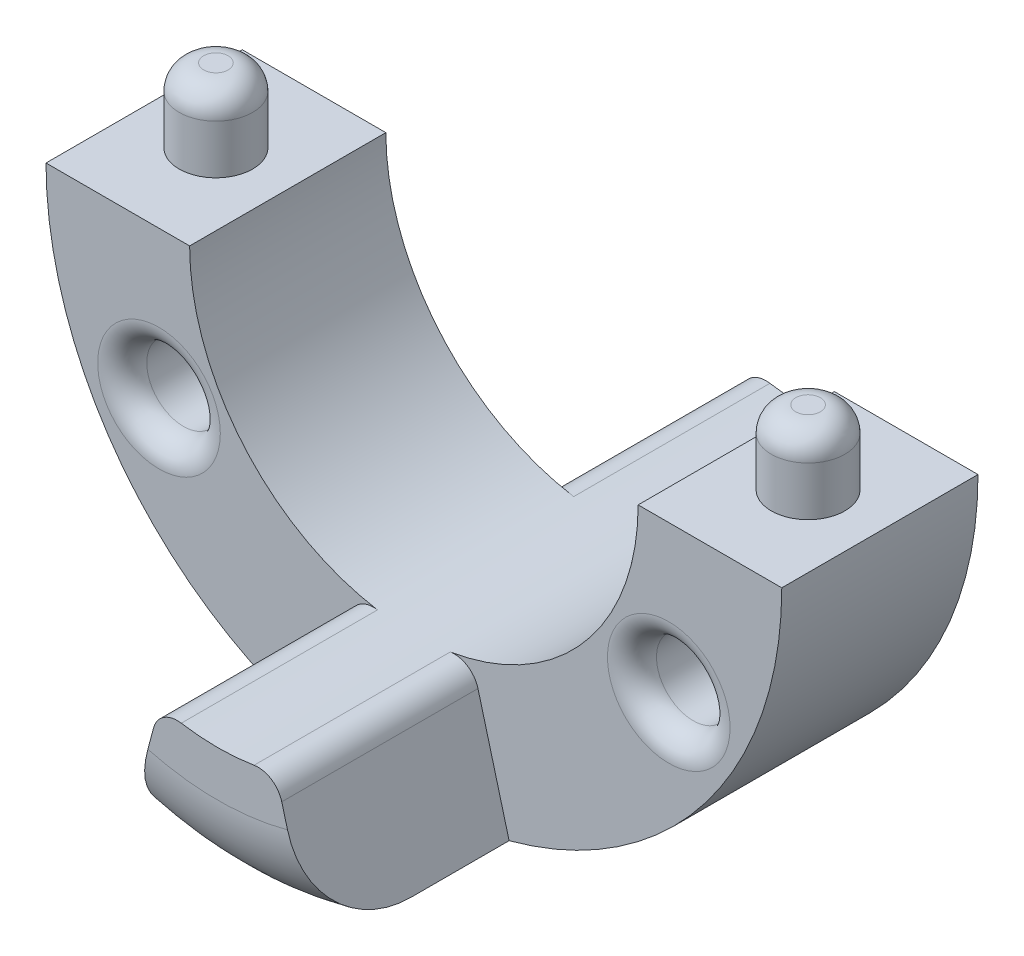
SolidWorks part; units mm, degrees
material "PET"
ref_plane "Front Plane" through (0, 0, 0) normal (0, 0, 1) x (1, 0, 0)
ref_plane "Top Plane" through (0, 0, 0) normal (0, 1, 0) x (1, 0, 0)
ref_plane "Right Plane" through (0, 0, 0) normal (1, 0, 0) x (0, 0, -1)
sketch "Sketch1" plane through (0, 0, 0) normal (0, 0, 1) x (1, 0, 0)
  line L0 (0, 0) -> (0, 2.286) construction
  line L1 (0, 2.625) -> (0, 3) construction
  line L2 (0, 2.625) -> (0, 2.286) construction
  circle A0 centre (0, 0) radius 2.286
  circle A1 centre (0, 0) radius 3.75
  circle A2 centre (0, 3) radius 0.375
  circle A3 centre (2.5981, -1.5) radius 0.375
  circle A4 centre (-2.5981, -1.5) radius 0.375
  point P15 (0, 0)
  dimension "D1" = 4.572
  dimension "D2" = 0.75
  dimension "D4" = 7.5
  dimension "D3" = 3
  dimension "D5" = 3
extrude "Boss-Extrude1" add sketch "Sketch1" along normal blind 2
sketch "Sketch2" plane through (0, 0, 2) normal (0, 0, 1) x (1, 0, 0)
  line L0 (-0.5917, -2.2081) -> (-0.9706, -3.6222)
  line L1 (0, 0) -> (0, -4.001) construction
  line L2 (0.5917, -2.2081) -> (0.9706, -3.6222)
  line L3 (-1.6164, 1.6164) -> (-2.6517, 2.6517)
  line L4 (-2.2081, 0.5917) -> (-3.6222, 0.9706)
  line L5 (2.2081, 0.5917) -> (3.6222, 0.9706)
  line L6 (1.6164, 1.6164) -> (2.6517, 2.6517)
  circle A0 centre (0, 0) radius 3.75 construction
  arc A1 (-0.9706, -3.6222) -> (0.9706, -3.6222) centre (0, 0) ccw
  arc A3 (-0.5917, -2.2081) -> (0.5917, -2.2081) centre (0, 0) ccw
  circle A4 centre (0, 0) radius 2.286 construction
  arc A5 (-2.6517, 2.6517) -> (-3.6222, 0.9706) centre (0, 0) ccw
  arc A6 (-1.6164, 1.6164) -> (-2.2081, 0.5917) centre (0, 0) ccw
  arc A7 (3.6222, 0.9706) -> (2.6517, 2.6517) centre (0, 0) ccw
  arc A8 (2.2081, 0.5917) -> (1.6164, 1.6164) centre (0, 0) ccw
  point P20 (0, 0)
  dimension "D1" = 15
  dimension "D2" = 3
extrude "Boss-Extrude2" add sketch "Sketch2" along normal blind 2 and the other way blind 4
fillet "Fillet1" radius 1 6 edges at (0, -3.75, -2) (-3.2476, 1.875, -2) (3.2476, 1.875, -2) (-3.2476, 1.875, 4) (0, -3.75, 4) (3.2476, 1.875, 4)
fillet "Fillet2" radius 0.25 6 edges at (0.375, 3, 0) (0.375, 3, 2) (2.9731, -1.5, 0) (2.9731, -1.5, 2) (-2.2231, -1.5, 0) (-2.2231, -1.5, 2)
fillet "Fillet3" radius 0.25 12 edges at (-2.2081, 0.5917, -1) (2.2081, 0.5917, -1) (0.5917, -2.2081, -1) (-0.5917, -2.2081, -1) (0.5917, -2.2081, 3) (-0.5917, -2.2081, 3) (-1.6164, 1.6164, -1) (1.6164, 1.6164, -1) (1.6164, 1.6164, 3) (2.2081, 0.5917, 3) (-1.6164, 1.6164, 3) (-2.2081, 0.5917, 3)
sketch "Sketch3" plane through (0, 0, 0) normal (0, 0, 1) x (1, 0, 0)
  line L1 (-3.75, 0) -> (3.75, 0)
  line L2 (-3.75, 0) -> (-3.75, 3.75)
  line L3 (-3.75, 3.75) -> (3.75, 3.75)
  line L4 (3.75, 0) -> (3.75, 3.75)
  arc A0 (-3.6222, 0.9706) -> (-0.9706, -3.6222) centre (0, 0) ccw construction
  arc A1 (0.9706, -3.6222) -> (3.6222, 0.9706) centre (0, 0) ccw construction
  arc A3 (2.6517, 2.6517) -> (-2.6517, 2.6517) centre (0, 0) ccw construction
extrude "Cut-Extrude1" cut sketch "Sketch3" against normal through all and the other way through all
sketch "Sketch4" plane through (0, 0, 0) normal (0, 1, 0) x (1, 0, 0)
  line L0 (-3.018, 0) -> (-3.018, -2) construction
  line L1 (-3.75, 0) -> (-2.286, 0) construction
  line L2 (-3.75, -2) -> (-2.286, -2) construction
  line L3 (-3.018, -2) -> (0, -2) construction
  line L4 (0, -2) -> (0, 0) construction
  circle A0 centre (-3.018, -1) radius 0.375
  circle A1 centre (3.018, -1) radius 0.375
  dimension "D1" = 0.75
extrude "Boss-Extrude3" add sketch "Sketch4" along normal blind 0.75
fillet "Fillet4" radius 0.25 2 edges at (3.393, 0.75, 1) (-3.393, 0.75, 1)
